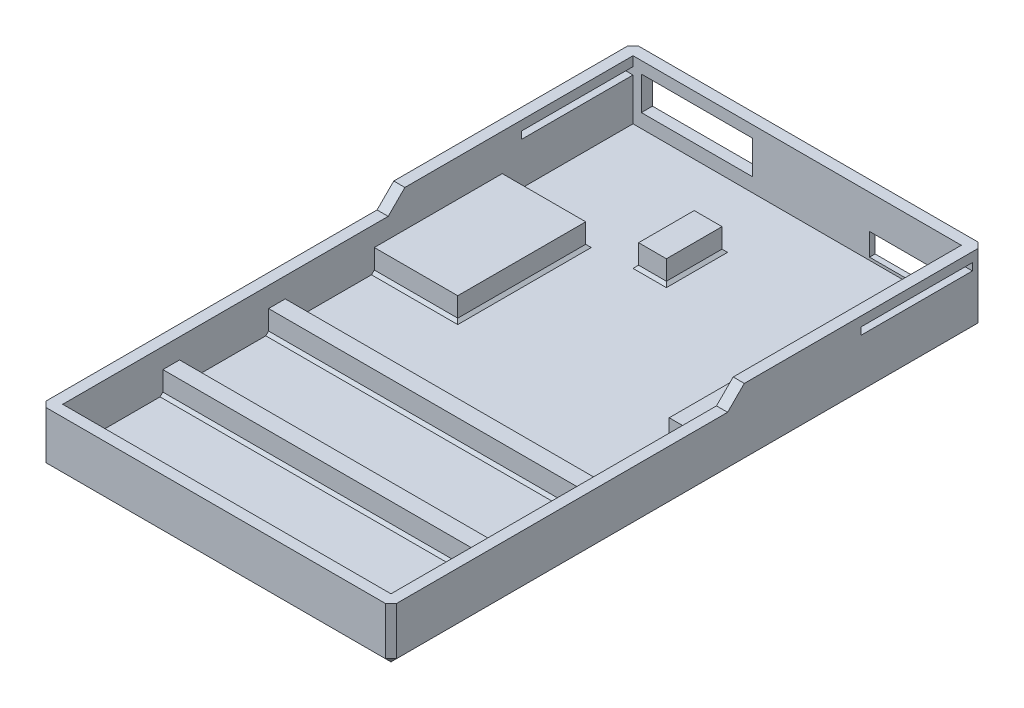
SolidWorks part; units mm, degrees
ref_plane "Front Plane" through (0, 0, 0) normal (0, 0, 1) x (1, 0, 0)
ref_plane "Top Plane" through (0, 0, 0) normal (0, 1, 0) x (1, 0, 0)
ref_plane "Right Plane" through (0, 0, 0) normal (1, 0, 0) x (0, 0, -1)
sketch "Sketch1" plane through (0, 0, 0) normal (0, 1, 0) x (1, 0, 0)
  line L1 (0, 0) -> (59, 0)
  line L2 (0, 0) -> (0, -102.5)
  line L3 (0, -102.5) -> (59, -102.5)
  line L4 (59, 0) -> (59, -102.5)
  dimension "D1" = 102.5
  dimension "D2" = 59
extrude "Boss-Extrude1" add sketch "Sketch1" along normal blind 2
sketch "Sketch2" plane through (0, 0, 0) normal (0, 1, 0) x (1, 0, 0)
  line L4 (0, 0) -> (0, -102.5)
  line L5 (0, -102.5) -> (59, -102.5)
  line L6 (59, -102.5) -> (59, 0)
  line L7 (59, 0) -> (0, 0)
  line L8 (0, 0) -> (0, -102.5)
  line L9 (0, -102.5) -> (59, -102.5)
  line L10 (59, -102.5) -> (59, 0)
  line L11 (59, 0) -> (0, 0)
  line L16 (-2, 2) -> (-2, -104.5)
  line L17 (-2, -104.5) -> (61, -104.5)
  line L18 (61, -104.5) -> (61, 2)
  line L19 (61, 2) -> (-2, 2)
  line L20 (-2, 2) -> (-2, -104.5)
  line L21 (-2, -104.5) -> (61, -104.5)
  line L22 (61, -104.5) -> (61, 2)
  line L23 (61, 2) -> (-2, 2)
  dimension "D1" = 0
  dimension "D2" = 2
extrude "Boss-Extrude2" add sketch "Sketch2" along normal blind 10.6 and the other way up to surface from surface other way up to face at (29.5, 0, 51.25) starting at face at (29.5, 2, 51.25)
sketch "Sketch4" plane through (0, 2, 0) normal (0, 1, 0) x (1, 0, 0)
  line L1 (0, -81.5) -> (59, -81.5)
  line L2 (0, -81.5) -> (0, -84.5)
  line L3 (0, -84.5) -> (59, -84.5)
  line L4 (59, -81.5) -> (59, -84.5)
  line L6 (0, 0) -> (0, -102.5) construction
  line L7 (59, -102.5) -> (59, 0) construction
  line L8 (0, -102.5) -> (59, -102.5) construction
  line L10 (0, -62.5) -> (59, -62.5)
  line L11 (0, -62.5) -> (0, -65.5)
  line L12 (0, -65.5) -> (59, -65.5)
  line L13 (59, -62.5) -> (59, -65.5)
  line L14 (0, 0) -> (0, -102.5) construction
  line L15 (59, -102.5) -> (59, 0) construction
  line L16 (15, -99.5) -> (18, -99.5)
  line L17 (15, -99.5) -> (15, -102.5)
  line L18 (15, -102.5) -> (18, -102.5)
  line L19 (18, -99.5) -> (18, -102.5)
  line L20 (34, -99.5) -> (37, -99.5)
  line L21 (34, -99.5) -> (34, -102.5)
  line L22 (34, -102.5) -> (37, -102.5)
  line L23 (37, -99.5) -> (37, -102.5)
  line L24 (53, -99.5) -> (56, -99.5)
  line L25 (53, -99.5) -> (53, -102.5)
  line L26 (53, -102.5) -> (56, -102.5)
  line L27 (56, -99.5) -> (56, -102.5)
  line L29 (15, -23.5) -> (0, -23.5)
  line L30 (15, -23.5) -> (15, -46.5)
  line L31 (15, -46.5) -> (0, -46.5)
  line L32 (0, -23.5) -> (0, -46.5)
  line L33 (59, 0) -> (0, 0) construction
  line L34 (53, -46.5) -> (59, -46.5)
  line L35 (53, -46.5) -> (53, -29.5)
  line L36 (53, -29.5) -> (59, -29.5)
  line L37 (59, -46.5) -> (59, -29.5)
  line L38 (59, 0) -> (56, 0)
  line L39 (59, 0) -> (59, -10)
  line L40 (59, -10) -> (56, -10)
  line L41 (56, 0) -> (56, -10)
  line L42 (23, -12) -> (28, -12)
  line L43 (23, -12) -> (23, -22)
  line L44 (23, -22) -> (28, -22)
  line L45 (28, -12) -> (28, -22)
  point P49 (25.5, -12)
  dimension "D1" = 3
  dimension "D2" = 59
  dimension "D3" = 18
  dimension "D4" = 3
  dimension "D5" = 59
  dimension "D6" = 19
  dimension "D7" = 3
  dimension "D8" = 3
  dimension "D9" = 3
  dimension "D10" = 3
  dimension "D11" = 19
  dimension "D12" = 19
  dimension "D13" = 23
  dimension "D14" = 15
  dimension "D15" = 19
  dimension "D16" = 17
  dimension "D17" = 6
  dimension "D18" = 10
  dimension "D19" = 3
  dimension "D20" = 10
  dimension "D21" = 5
  dimension "D22" = 12
  dimension "D23" = 23
extrude "Boss-Extrude3" add sketch "Sketch4" along normal blind 4 from surface starting at face at (29.5, 2, 51.25)
sketch "Sketch5" plane through (0, 0, -2) normal (0, 0, -1) x (-1, 0, 0)
  line L0 (0, 6) -> (-15, 6) construction
  line L1 (0, 6) -> (-15, 6) construction
  line L9 (-1.5, 10.5) -> (-21.5, 10.5)
  line L10 (-1.5, 10.5) -> (-1.5, 4.5)
  line L11 (-1.5, 4.5) -> (-21.5, 4.5)
  line L12 (-21.5, 10.5) -> (-21.5, 4.5)
  line L13 (-59, 12.6) -> (-59, 6) construction
  line L14 (-53.3, 6.5) -> (-42.5, 6.5)
  line L15 (-53.3, 6.5) -> (-53.3, 2.5)
  line L16 (-53.3, 2.5) -> (-42.5, 2.5)
  line L17 (-42.5, 6.5) -> (-42.5, 2.5)
  dimension "D1" = 6
  dimension "D2" = 20
  dimension "D3" = 1.5
  dimension "D4" = 4
  dimension "D5" = 10.8
  dimension "D6" = 0.5
  dimension "D7" = 5.7
  dimension "D8" = 1.5
extrude "Cut-Extrude1" cut sketch "Sketch5" against normal up to next
chamfer "Chamfer1" distance 0.5 angle 45 25 edges at (56, 2, 29.5) (56, 2, 46.5) (53, 2, 38) (57.5, 2, 10) (56, 2, 5) (7.5, 2, 46.5) (15, 2, 35) (7.5, 2, 23.5) (23, 2, 17) (25.5, 2, 12) (28, 2, 17) (25.5, 2, 22) (53, 2, 101) (56, 2, 101) (54.5, 2, 99.5) (15, 2, 101) (16.5, 2, 99.5) (18, 2, 101) (37, 2, 101) (34, 2, 101) (35.5, 2, 99.5) (29.5, 2, 81.5) (29.5, 2, 84.5) (29.5, 2, 65.5) (29.5, 2, 62.5)
chamfer "Chamfer2" distance 1 angle 45 12 edges at (47.9, 2.5, -2) (42.5, 4.5, -2) (47.9, 6.5, -2) (53.3, 4.5, -2) (61, 6.3, 104.5) (-2, 6.3, 104.5) (61, 6.3, -2) (-2, 6.3, -2) (-2, 0, 51.25) (29.5, 0, 104.5) (61, 0, 51.25) (29.5, 0, -2)
sketch "Sketch6" plane through (0, 0, 0) normal (0, 0, 1) x (1, 0, 0)
  line L0 (0, 10.9) -> (-2, 10.9)
  line L1 (0, 12.6) -> (0, 2) construction
  line L2 (-2, 10.9) -> (-2, 9.6)
  line L3 (-2, 9.6) -> (0, 9.6)
  line L4 (0, 10.9) -> (0, 9.6)
  line L5 (59, 12.6) -> (0, 12.6) construction
  line L9 (59, 12.6) -> (0, 12.6) construction
  line L10 (29.5, 12.6) -> (29.5, 2) construction
  line L11 (55.5, 2) -> (0, 2) construction
  line L12 (59, 10.9) -> (59, 9.6)
  line L13 (61, 9.6) -> (59, 9.6)
  line L14 (61, 10.9) -> (61, 9.6)
  line L15 (59, 10.9) -> (61, 10.9)
  dimension "D1" = 1.7
  dimension "D2" = 1.3
  dimension "D3" = 2
extrude "Cut-Extrude2" cut sketch "Sketch6" along normal blind 20
sketch "Sketch7" plane through (0, 0, 0) normal (1, 0, 0) x (0, 0, -1)
  line L1 (-104.5, 12.6) -> (-44, 12.6)
  line L2 (-104.5, 12.6) -> (-104.5, 9.6)
  line L3 (-104.5, 9.6) -> (-44, 9.6)
  line L4 (-44, 12.6) -> (-44, 9.6)
  dimension "D1" = 3
  dimension "D2" = 60.5
extrude "Cut-Extrude3" cut sketch "Sketch7" along normal through all both and the other way through all
chamfer "Chamfer3" distance 3 angle 45 2 edges at (-1, 12.6, 44) (60, 12.6, 44)
